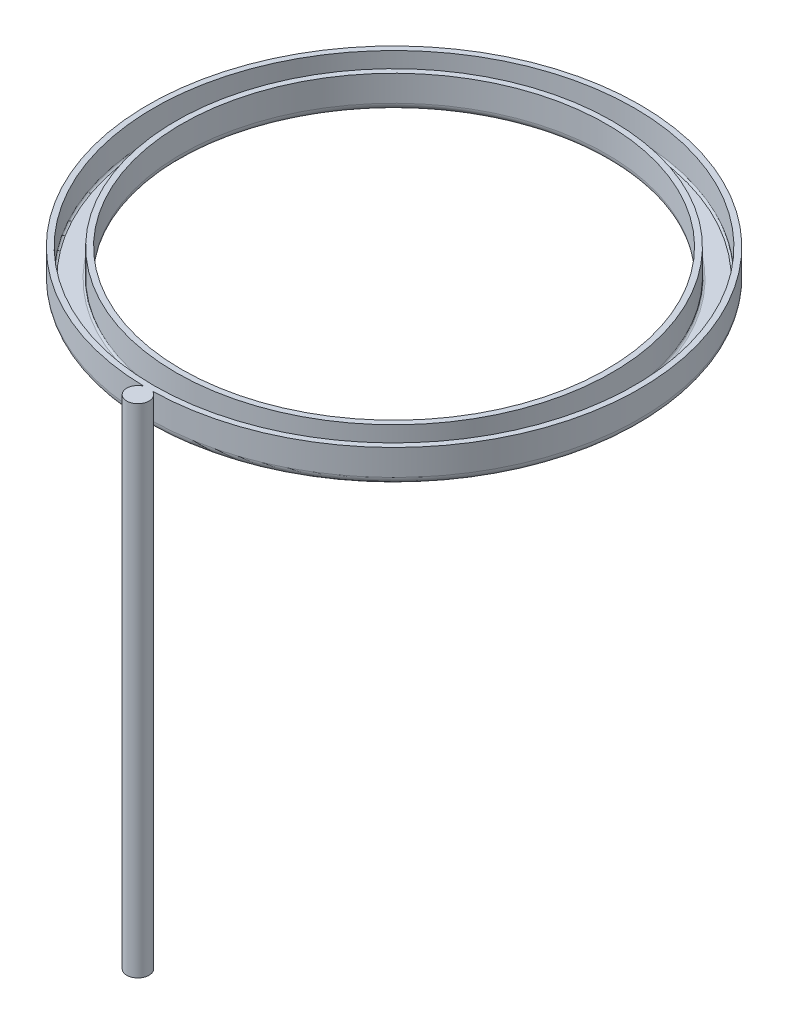
SolidWorks part; units mm, degrees
material "Chrome Stainless Steel"
ref_plane "Front Plane" through (0, 0, 0) normal (0, 0, 1) x (1, 0, 0)
ref_plane "Top Plane" through (0, 0, 0) normal (0, 1, 0) x (1, 0, 0)
ref_plane "Right Plane" through (0, 0, 0) normal (1, 0, 0) x (0, 0, -1)
sketch "Sketch1" plane through (0, 0, 0) normal (0, 0, 1) x (1, 0, 0)
  line L0 (0, 22.5592) -> (0, -20.7251) construction
  line L1 (0, -55) -> (0, 55) construction
  line L2 (-6.625, 0.9) -> (-6.625, 0.2)
  line L3 (55, 0) -> (-55, 0) construction
  line L4 (-6.425, 0) -> (-5.925, 0)
  line L5 (-5.725, 0.2) -> (-5.725, 0.9)
  arc A0 (-5.725, 0.2) -> (-5.925, 0) centre (-5.925, 0.2) cw
  arc A1 (-6.625, 0.2) -> (-6.425, 0) centre (-6.425, 0.2) ccw
  point P13 (-5.725, 0)
  point P16 (-6.625, 0)
  dimension "D4" = 0.2
  dimension "D1" = 0.9
  dimension "D2" = 0.9
  dimension "D3" = 13.25
revolve "Revolve-Thin1" add sketch "Sketch1" angle 360 about L0 wall 0.15
ref_plane "Plane1" through (0, 0, 6.5) normal (0, 0, 1) x (1, 0, 0)
ref_axis "Axis1" through (0, 0.7875, 6.5) along (0, -1, 0)
ref_plane "Plane2" through (2.0891, 0, 5.7396) normal (0.342, 0, 0.9397) x (0.9397, 0, -0.342)
sketch "Sketch2" plane through (2.0891, 0, 5.7396) normal (0.342, 0, 0.9397) x (0.9397, 0, -0.342)
  line L0 (-2.2231, -10) -> (-2.2231, -0.6)
  line L1 (-2.2231, 0.7875) -> (-2.2231, -0.0375) construction
  line L2 (-1.9231, -0.3) -> (2.7769, -0.3)
  line L3 (7.425, 0) -> (-7.425, 0) construction
  arc A0 (-2.2231, -0.6) -> (-1.9231, -0.3) centre (-1.9231, -0.6) cw
  point P7 (-2.2231, -0.3)
  dimension "D1" = 0.3
  dimension "D2" = 0.3
  dimension "D3" = 5
  dimension "D4" = 10
sketch3d "3DSketch1"
  circle A0 centre (0, -10, 6.5) radius 0.3
  point P3 (0, -9.7, 6.5)
  dimension "D1" = 0.6
sweep "Sweep1" [suppressed] add profiles "3DSketch1" path "Sketch2"
sketch "Sketch3" plane through (0, 0, 0) normal (0, 1, 0) x (1, 0, 0)
  line L0 (0, -0.495) -> (0, 0.495) construction
  line L1 (-0.495, 0) -> (0.495, 0) construction
  circle A0 centre (0, -6.9) radius 0.3
  dimension "D2" = 0.6
  dimension "D1" = 6.9
extrude "Extrude1" add sketch "Sketch3" along normal blind 0.9 and the other way blind 12.5
